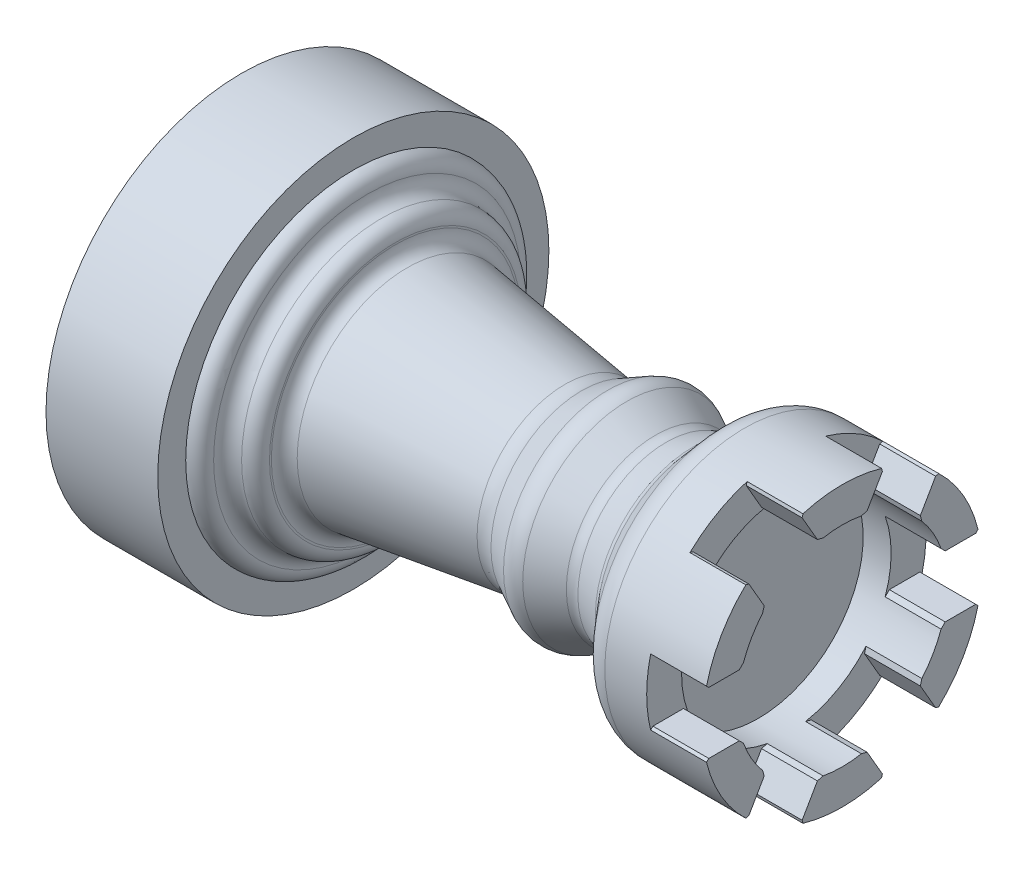
SolidWorks part; units mm, degrees
material "Latão"
ref_plane "Plano frontal" through (0, 0, 0) normal (0, 0, 1) x (1, 0, 0)
ref_plane "Plano superior" through (0, 0, 0) normal (0, 1, 0) x (1, 0, 0)
ref_plane "Plano direito" through (0, 0, 0) normal (1, 0, 0) x (0, 0, -1)
sketch "Esboço1" plane through (0, 0, 0) normal (0, 0, 1) x (1, 0, 0)
  line L0 (3, 5) -> (4, 5)
  line L1 (0, 0) -> (0, 6)
  line L2 (0, 6) -> (3, 6)
  line L3 (3, 6) -> (3, 5)
  line L4 (4, 5) -> (4, 4)
  line L5 (13.5, 3.0999) -> (11.9443, 3.902)
  line L6 (11.9443, 3.902) -> (10.3887, 3.0999)
  line L7 (14.7724, 3.5369) -> (15.7453, 4.6561)
  line L8 (16.5, 5) -> (20, 5)
  line L9 (20, 5) -> (20, 3.75)
  line L10 (20, 3.75) -> (17, 3.75)
  line L11 (17, 3.75) -> (17, 0)
  line L12 (4, 4) -> (10.3887, 3.0999)
  line L13 (0, 0) -> (17, 0)
  line L14 (11.9443, 3.902) -> (11.9443, 6) construction
  arc A1 (16.5, 5) -> (15.7453, 4.6561) centre (16.5, 4) ccw
  arc A2 (13.5, 3.0999) -> (14.7724, 3.5369) centre (7.6438, 22.2233) ccw
  dimension "D6" = 1
  dimension "D8" = 41
  dimension "D2" = 1
  dimension "D1" = 20
  dimension "D3" = 3
  dimension "D4" = 6
  dimension "D5" = 1
  dimension "D7" = 3.5
  dimension "D10" = 5
  dimension "D11" = 3.75
  dimension "D12" = 3
  dimension "D13" = 3.5
revolve "Revolução1" add sketch "Esboço1" angle 360 about L13
sketch "Esboço2" plane through (20, 0, 0) normal (1, 0, 0) x (0, 0, -1)
  line L1 (6.15, -1.1) -> (-6.15, -1.1)
  line L2 (6.15, -1.1) -> (6.15, 1.1)
  line L3 (6.15, 1.1) -> (-6.15, 1.1)
  line L4 (-6.15, -1.1) -> (-6.15, 1.1)
  line L5 (6.15, -1.1) -> (-6.15, 1.1) construction
  line L6 (6.15, 1.1) -> (-6.15, -1.1) construction
  point P0 (0, 0)
  dimension "D1" = 2.2
  dimension "D2" = 12.3
extrude "Corte-extrusão1" cut sketch "Esboço2" against normal blind 2
fillet "Filete3" radius 0.5 4 edges at (14.7724, 0, 3.5369) (13.5, 0, 3.0999) (3, 0, 5) (4, 0, 4)
fillet "Filete4" radius 0.5 2 edges at (4, 0, 5) (3, 0, 6)
chamfer "Chanfro1" distance 0.35 angle 45 1 edges at (0, 0, 6)
fillet "Filete5" radius 0.75 1 edges at (11.9443, 0, 3.902)
pattern_circular "PadrãoCircular1" count 3 over 360 about axis through (0, 0, 0) along (-1, 0, 0) of "Corte-extrusão1"
fillet "Filete6" radius 1 1 edges at (10.3887, 0, 3.0999)
chamfer "Chanfro2" distance 0.1 angle 45 24 edges at (19, -2.5547, -2.7451) (19, 2.5547, -2.7451) (19, -3.6547, 0.8399) (19, -1.1, 3.585) (19, -1.1, 4.8775) (19, 4.774, 1.4861) (19, 3.674, 3.3914) (19, 4.774, -1.4861) (19, 3.674, -3.3914) (19, -1.1, -3.585) (19, -3.6547, -0.8399) (19, 1.1, 4.8775) (19, -4.774, 1.4861) (19, -2.5547, 2.7451) (19, -3.674, 3.3914) (19, -1.1, -4.8775) (19, 1.1, -3.585) (19, 1.1, -4.8775) (19, 3.6547, -0.8399) (19, 3.6547, 0.8399) (19, -3.674, -3.3914) (19, -4.774, -1.4861) (19, 1.1, 3.585) (19, 2.5547, 2.7451) first distance on face at (19, -3.1144, -3.0683) first distance on face at (19, 3.1144, -3.0683) first distance on face at (19, -4.2144, 1.163) first distance on face at (19, -1.1, 4.2313) first distance on face at (19, 4.2144, 1.163) first distance on face at (19, 3.1144, 3.0683) first distance on face at (19, 4.2144, -1.163) first distance on face at (19, -1.1, -4.2313) first distance on face at (19, -4.2144, -1.163) first distance on face at (19, 1.1, 4.2313) first distance on face at (19, -3.1144, 3.0683) first distance on face at (19, 1.1, -4.2313)
sketch "Sketch1" plane through (0, 0, 0) normal (-1, 0, 0) x (0, 0, 1)
  circle A0 centre (0, 0) radius 7
extrude "Boss-Extrude1" add sketch "Sketch1" against normal blind 2.5
extrude "Boss-Extrude2" add sketch "Sketch1<2>" along normal blind 1.5
sketch "Sketch1<2>" plane through (0, 0, 0) normal (-1, 0, 0) x (0, 0, 1) same geometry as "Sketch1"
sketch "Sketch3" plane through (-1.5, 0, 0) normal (-1, 0, 0) x (0, 0, 1)
  circle A0 centre (0, 0) radius 6.05
  dimension "D1" = 12.1
extrude "Cut-Extrude1" cut sketch "Sketch3" against normal blind 3.2
